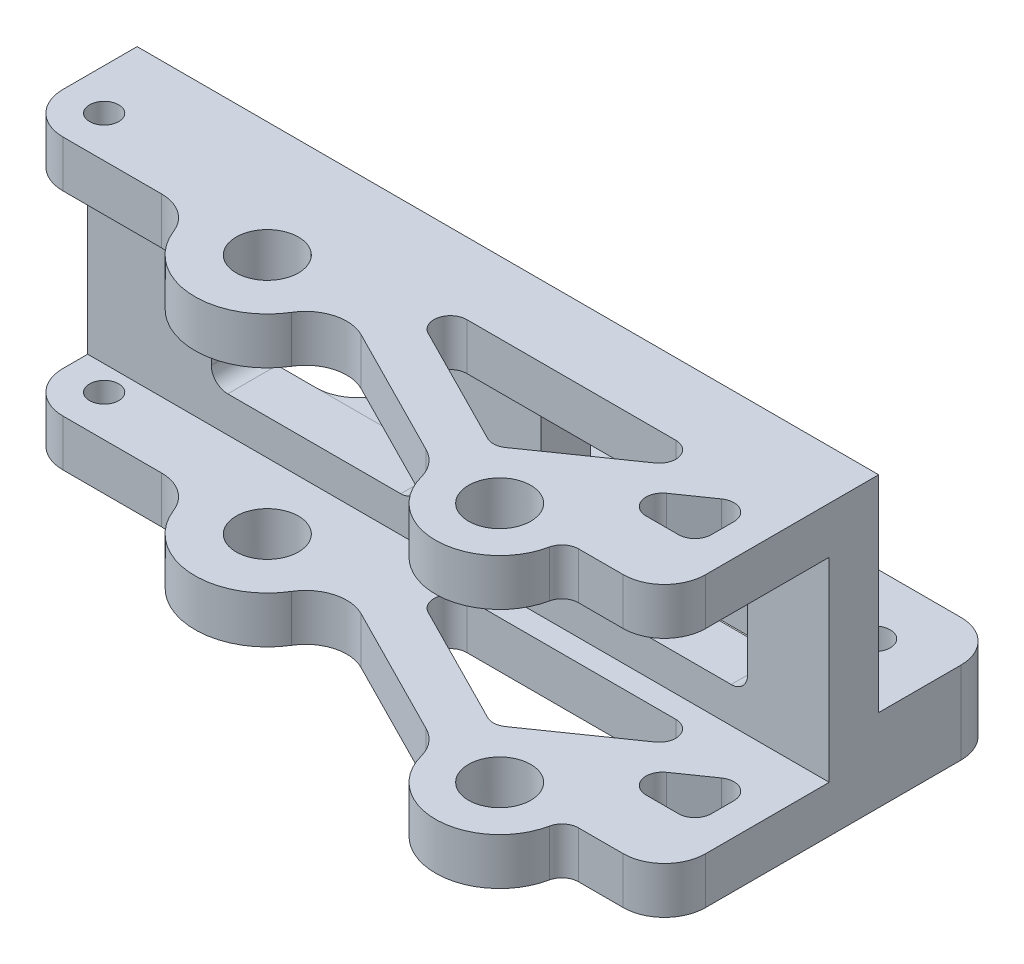
SolidWorks part; units mm, degrees
ref_plane "Front Plane" through (0, 0, 0) normal (0, 0, 1) x (1, 0, 0)
ref_plane "Top Plane" through (0, 0, 0) normal (0, 1, 0) x (1, 0, 0)
ref_plane "Right Plane" through (0, 0, 0) normal (1, 0, 0) x (0, 0, -1)
sketch "Sketch1" plane through (0, 0, 0) normal (0, 0, 1) x (1, 0, 0)
  line L1 (57.15, -22.225) -> (-57.15, -22.225)
  line L2 (57.15, -22.225) -> (57.15, 22.225)
  line L3 (57.15, 22.225) -> (-57.15, 22.225)
  line L4 (-57.15, -22.225) -> (-57.15, 22.225)
  line L5 (57.15, -22.225) -> (-57.15, 22.225) construction
  line L6 (57.15, 22.225) -> (-57.15, -22.225) construction
  point P0 (0, 0)
  dimension "D1" = 44.45
  dimension "D2" = 114.3
extrude "Boss-Extrude1" add sketch "Sketch1" along normal blind 64.77
sketch "Sketch2" plane through (0, 0, 64.77) normal (0, 0, 1) x (1, 0, 0)
  line L0 (-57.15, 22.225) -> (-57.15, -22.225) construction
  line L1 (57.15, -15.025) -> (-57.15, -15.025)
  line L2 (57.15, -15.025) -> (57.15, 15.025)
  line L3 (57.15, 15.025) -> (-57.15, 15.025)
  line L4 (-57.15, -15.025) -> (-57.15, 15.025)
  line L5 (57.15, -15.025) -> (-57.15, 15.025) construction
  line L6 (57.15, 15.025) -> (-57.15, -15.025) construction
  line L7 (57.15, 22.225) -> (-57.15, 22.225) construction
  point P0 (0, 0)
  dimension "D1" = 7.2
extrude "Cut-Extrude2" cut sketch "Sketch2" against normal blind 35.56
sketch "Sketch3" plane through (0, 0, 0) normal (0, 0, -1) x (-1, 0, 0)
  line L0 (-57.15, -22.225) -> (-57.15, 22.225) construction
  line L1 (57.15, 22.225) -> (-57.15, 22.225)
  line L2 (57.15, 22.225) -> (57.15, -9.525)
  line L3 (57.15, -9.525) -> (-57.15, -9.525)
  line L4 (-57.15, 22.225) -> (-57.15, -9.525)
  line L5 (57.15, -22.225) -> (-57.15, -22.225) construction
  dimension "D1" = 12.7
extrude "Cut-Extrude3" cut sketch "Sketch3" against normal blind 21.59
sketch "Sketch5" plane through (0, -22.225, 0) normal (0, -1, 0) x (1, 0, 0)
  line L0 (-3.81, 12.06) -> (46.99, 12.06) construction
  line L1 (57.15, 21.59) -> (-57.15, 21.59) construction
  line L2 (57.15, 64.77) -> (57.15, 0) construction
  circle A0 centre (-3.81, 12.06) radius 2.415
  circle A1 centre (46.99, 12.06) radius 2.415
  dimension "D3" = 4.83
  dimension "D4" = 10.16
  dimension "D1" = 9.53
  dimension "D2" = 50.8
extrude "Cut-Extrude4" cut sketch "Sketch5" against normal blind 25.4
sketch "Sketch7" plane through (0, -22.225, 0) normal (0, -1, 0) x (1, 0, 0)
  line L0 (57.15, 64.77) -> (57.15, 0) construction
  line L1 (-57.15, 0) -> (57.15, 0) construction
  circle A0 centre (31.75, 54.61) radius 4.8
  circle A1 centre (-19.3, 39.37) radius 4.8
  dimension "D1" = 9.6
  dimension "D2" = 25.4
  dimension "D3" = 39.37
  dimension "D4" = 9.6
  dimension "D5" = 51.05
  dimension "D6" = 15.24
extrude "Cut-Extrude6" cut sketch "Sketch7" against normal up to surface (44.45 mm away) up to face at (0, 22.225, 43.18)
sketch "Sketch9" plane through (0, 0, 29.21) normal (0, 0, 1) x (1, 0, 0)
  line L5 (57.15, 15.025) -> (-57.15, 15.025) construction
  line L6 (-38.1, 15.025) -> (-6.35, 15.025)
  line L7 (-38.1, 15.025) -> (-38.1, -15.025)
  line L8 (-38.1, -15.025) -> (-6.35, -15.025)
  line L9 (-6.35, 15.025) -> (-6.35, -15.025)
  line L10 (-57.15, -15.025) -> (57.15, -15.025) construction
  line L11 (-57.15, 15.025) -> (-57.15, -15.025) construction
  line L12 (57.15, -15.025) -> (57.15, 15.025) construction
  dimension "D1" = 63.5
  dimension "25in" = 19.05
extrude "Cut-Extrude7" cut sketch "Sketch9" against normal through all both and the other way through all
sketch "Sketch16" plane through (0, -22.225, 0) normal (0, -1, 0) x (1, 0, 0)
  line L1 (-38.1, 29.21) -> (-57.15, 29.21) construction
  line L4 (-30.45, 39.37) -> (-30.45, 29.21)
  line L8 (-57.15, 64.77) -> (57.15, 64.77)
  line L9 (57.15, 64.77) -> (57.15, 54.61)
  line L10 (57.15, 64.77) -> (57.15, 0) construction
  line L11 (-8.15, 39.37) -> (21.87, 54.61)
  line L12 (41.63, 54.61) -> (57.15, 54.61)
  line L13 (-49.091, 29.21) -> (-57.15, 29.21)
  line L14 (-30.45, 29.21) -> (-49.091, 29.21)
  line L15 (-57.15, 29.21) -> (-57.15, 64.77)
  arc A2 (41.63, 54.61) -> (21.87, 54.61) centre (31.75, 54.61) ccw
  arc A3 (-8.15, 39.37) -> (-30.45, 39.37) centre (-19.3, 39.37) ccw
  circle A4 centre (-19.3, 39.37) radius 4.8 construction
  circle A5 centre (31.75, 54.61) radius 4.8 construction
  dimension "D1" = 6.35
  dimension "D2" = 5.08
  dimension "D3" = 10.16
extrude "Cut-Extrude8" cut sketch "Sketch16" against normal through all
sketch "Sketch14" plane through (-6.35, 0, 0) normal (-1, 0, 0) x (0, 0, 1)
  line L0 (0, -15.025) -> (29.21, -15.025) construction
  line L1 (21.59, -9.525) -> (0, -9.525)
  line L2 (21.59, -9.525) -> (21.59, -15.025)
  line L3 (21.59, -15.025) -> (0, -15.025)
  line L4 (0, -9.525) -> (0, -15.025)
extrude "Boss-Extrude2" add sketch "Sketch14" along normal up to next
sketch "Sketch17" plane through (0, 0, 21.59) normal (0, 0, 1) x (1, 0, 0)
  line L1 (-6.35, -15.025) -> (-38.1, -15.025)
  line L2 (-6.35, -15.025) -> (-6.35, -9.525)
  line L3 (-6.35, -9.525) -> (-38.1, -9.525)
  line L4 (-38.1, -15.025) -> (-38.1, -9.525)
extrude "Boss-Extrude3" add sketch "Sketch17" along normal up to surface (7.62 mm away) up to face at (25.4, 0, 29.21)
sketch "Sketch25" plane through (-30.45, 0, 0) normal (-1, 0, 0) x (0, 0, 1)
  line L0 (39.37, 15.025) -> (29.21, 15.025) construction
  line L1 (29.21, 22.225) -> (39.37, 22.225)
  line L2 (29.21, 22.225) -> (29.21, 15.025)
  line L3 (29.21, 15.025) -> (39.37, 15.025)
  line L4 (39.37, 22.225) -> (39.37, 15.025)
  line L5 (39.37, -22.225) -> (50.52, -22.225) construction
  line L6 (29.21, -15.025) -> (39.37, -15.025)
  line L7 (29.21, -15.025) -> (29.21, -22.225)
  line L8 (29.21, -22.225) -> (39.37, -22.225)
  line L9 (39.37, -15.025) -> (39.37, -22.225)
  dimension "D1" = 10.16
extrude "Boss-Extrude5" add sketch "Sketch25" along normal up to surface (26.7 mm away) up to face at (-57.15, -3.175, 16.9333)
sketch "Sketch28" plane through (0, -22.225, 0) normal (0, -1, 0) x (-1, 0, 0)
sketch "Sketch30" plane through (0, -22.225, 0) normal (0, -1, 0) x (-1, 0, 0)
  line L2 (57.15, -39.37) -> (30.45, -39.37) construction
  line L4 (57.15, -39.37) -> (57.15, 0) construction
  point P10 (50.8, -33.02)
  dimension "D1" = 6.35
  dimension "D2" = 6.35
hole_wizard "#8 Clearance Hole1" positions "Sketch30" profile "Sketch29" hole size "#8" standard "ANSI Inch" end condition through all
sketch "Sketch29" plane through (-50.8, -22.225, 33.02) normal (1, 0, 0) x (0, 0, -1)
  line L0 (0, 0) -> (0, 44.45)
  line L1 (0, 44.45) -> (2.2479, 44.45)
  line L2 (2.2479, 44.45) -> (2.2479, 0)
  line L5 (2.2479, 0) -> (0, 0)
  line L11 (0, -6.35) -> (0, 107.95) construction
  dimension "Thru Hole Dia." = 4.4958
  dimension "Thru Hole Depth" = 44.45
sketch "Sketch31" plane through (0, 0, 0) normal (0, 0, -1) x (-1, 0, 0)
  line L1 (-57.15, -9.525) -> (57.15, -9.525)
  line L2 (-57.15, -9.525) -> (-57.15, -22.225)
  line L3 (-57.15, -22.225) -> (57.15, -22.225)
  line L4 (57.15, -9.525) -> (57.15, -22.225)
extrude "Cut-Extrude9" cut sketch "Sketch31" against normal blind 2.54
sketch "Sketch32" plane through (0, -22.225, 0) normal (0, -1, 0) x (1, 0, 0)
  line L0 (-5.9182, 32.621) -> (23.5316, 47.5715)
  line L1 (23.5316, 47.5715) -> (45.0021, 32.621)
  line L2 (45.0021, 32.621) -> (-5.9182, 32.621)
  line L3 (-8.15, 39.37) -> (21.87, 54.61) construction
  line L4 (36.6419, 45.0215) -> (52.2621, 45.0215)
  line L5 (52.2621, 45.0215) -> (52.2621, 34.1447)
  line L6 (52.2621, 34.1447) -> (36.6419, 45.0215)
  line L7 (57.15, 2.54) -> (-57.15, 2.54) construction
  line L8 (-57.15, 2.54) -> (-7.2674, 2.54)
  line L9 (-57.15, 2.54) -> (-57.15, 21.59)
  line L10 (-57.15, 21.59) -> (-26.9888, 21.59)
  line L11 (-7.2674, 2.54) -> (-26.9888, 21.59)
  line L12 (-57.15, 39.37) -> (-57.15, 2.54) construction
  line L16 (-38.1, 21.59) -> (-57.15, 21.59) construction
  dimension "D1" = 30.1612
extrude "Cut-Extrude10" cut sketch "Sketch32" against normal through all
fillet "Fillet2" radius 2.54 2 edges at (41.63, 18.625, 54.61) (41.63, -18.625, 54.61)
fillet "Fillet3" radius 6.35 13 edges at (57.15, -15.875, 2.54) (57.15, 18.625, 54.61) (57.15, -18.625, 54.61) (21.87, -18.625, 54.61) (21.87, 18.625, 54.61) (-8.15, 18.625, 39.37) (-8.15, -18.625, 39.37) (-7.2674, -15.875, 2.54) (-26.9888, -15.875, 21.59) (-57.15, -18.625, 39.37) (-57.15, 18.625, 39.37) (-30.45, 18.625, 39.37) (-30.45, -18.625, 39.37)
sketch "Sketch33" plane through (0, -9.525, 0) normal (0, 1, 0) x (1, 0, 0)
  line L1 (57.15, -21.59) -> (-40.8747, -21.59)
  line L2 (57.15, -21.59) -> (57.15, 0)
  line L3 (57.15, 0) -> (-40.8747, 0)
  line L4 (-40.8747, -21.59) -> (-40.8747, 0)
split line "Split Line1"
sketch "Sketch35" plane through (0, -22.225, 0) normal (0, -1, 0) x (1, 0, 0)
  line L0 (-4.4635, 21.59) -> (47.1888, 21.59)
  line L1 (47.1888, 21.59) -> (34.29, 8.6912)
  line L2 (34.29, 8.6912) -> (8.89, 8.6912)
  line L3 (8.89, 8.6912) -> (-4.4635, 21.59)
  line L4 (-9.113, 4.3228) -> (-25.1431, 19.8072) construction
  line L5 (-4.7013, 2.54) -> (50.8, 2.54) construction
  line L6 (-29.5549, 21.59) -> (-6.35, 21.59) construction
  line L7 (-3.81, 12.06) -> (46.99, 12.06) construction
  point P14 (21.59, 12.06)
  point P15 (21.59, 8.6912)
  dimension "D1" = 225
  dimension "D2" = 25.4
extrude "Cut-Extrude11" cut sketch "Sketch35" against normal through all
sketch "Sketch36" plane through (0, 0, 29.21) normal (0, 0, 1) x (1, 0, 0)
  line L0 (18.9406, 15.025) -> (-1.4542, 15.025) construction
  line L1 (12.7, 15.025) -> (44.575, 15.025)
  line L2 (12.7, 15.025) -> (12.7, -9.525)
  line L3 (12.7, -9.525) -> (44.575, -9.525)
  line L4 (44.575, 15.025) -> (44.575, -9.525)
  line L5 (-6.35, -9.525) -> (-6.35, 15.025) construction
  dimension ".5" = 19.05
extrude "Cut-Extrude12" cut sketch "Sketch36" against normal through all
fillet "Fillet1" radius 2.54 16 edges at (-5.9182, 18.625, 32.621) (45.0021, 18.625, 32.621) (23.5316, 18.625, 47.5715) (36.6419, 18.625, 45.0215) (52.2621, 18.625, 45.0215) (52.2621, 18.625, 34.1447) (52.2621, -18.625, 45.0215) (52.2621, -18.625, 34.1447) (36.6419, -18.625, 45.0215) (45.0021, -18.625, 32.621) (23.5316, -18.625, 47.5715) (-5.9182, -18.625, 32.621) (47.1888, -15.875, 21.59) (34.29, -15.875, 8.6912) (8.89, -15.875, 8.6912) (-4.4635, -15.875, 21.59)
sketch "Sketch34" plane through (0, 0, 21.59) normal (0, 0, -1) x (-1, 0, 0)
  line L0 (57.15, -22.225) -> (57.15, 22.225) construction
  line L1 (-57.15, -9.525) -> (57.15, -9.525)
  line L2 (-57.15, -9.525) -> (-57.15, 9.525)
  line L3 (-57.15, 9.525) -> (57.15, 9.525)
  line L4 (57.15, -9.525) -> (57.15, 9.525)
  dimension "D1" = 19.05
split line "Split Line2"
fillet "Fillet4" radius 2.54 8 edges at (44.575, 15.025, 25.4) (12.7, 15.025, 25.4) (-6.35, 15.025, 25.4) (-38.1, 15.025, 25.4) (-38.1, -9.525, 25.4) (-6.35, -9.525, 25.4) (12.7, -9.525, 25.4) (44.575, -9.525, 25.4)
